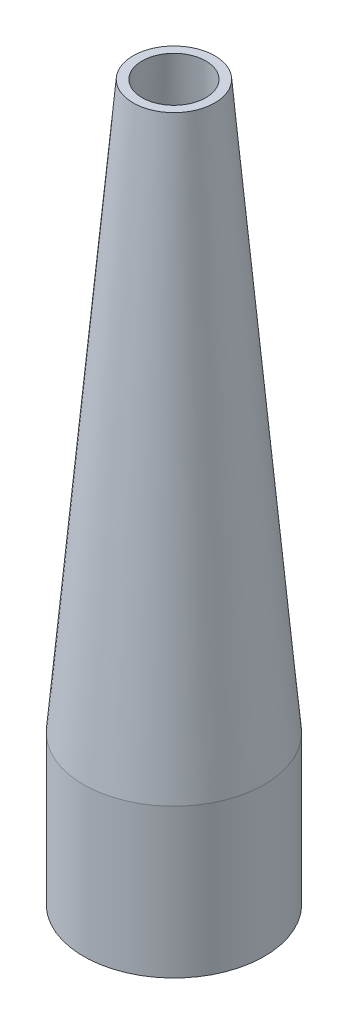
SolidWorks part; units mm, degrees
material "S-Glass Fiber"
ref_plane "Front Plane" through (0, 0, 0) normal (0, 0, 1) x (1, 0, 0)
ref_plane "Top Plane" through (0, 0, 0) normal (0, 1, 0) x (1, 0, 0)
ref_plane "Right Plane" through (0, 0, 0) normal (1, 0, 0) x (0, 0, -1)
sketch "Sketch1" plane through (0, 0, 0) normal (0, 0, 1) x (1, 0, 0)
  line L0 (0, 0) -> (0, 49.1635) construction
  line L1 (9.525, 49.1635) -> (12.2022, 49.1635)
  line L2 (12.2022, 49.1635) -> (26.9875, -119.8334)
  line L3 (26.9875, -119.8334) -> (24.3103, -119.8334)
  line L4 (24.3103, -119.8334) -> (9.525, 49.1635)
  line L5 (26.9875, -164.2834) -> (26.9875, -167.4584) construction
  line L6 (24.3103, -119.8334) -> (26.9875, -119.8334)
  line L7 (24.3103, -119.8334) -> (24.3103, -164.2834)
  line L8 (24.3103, -164.2834) -> (26.9875, -164.2834)
  line L9 (26.9875, -119.8334) -> (26.9875, -164.2834)
  point P11 (0, 0)
  point P14 (26.9875, -164.2834)
  point P17 (24.3103, -164.2834)
revolve "Revolve1" add sketch "Sketch1" angle 360 about L0 region at (18.2563, -35.335, 0) region at (25.6489, -142.0584, 0)
